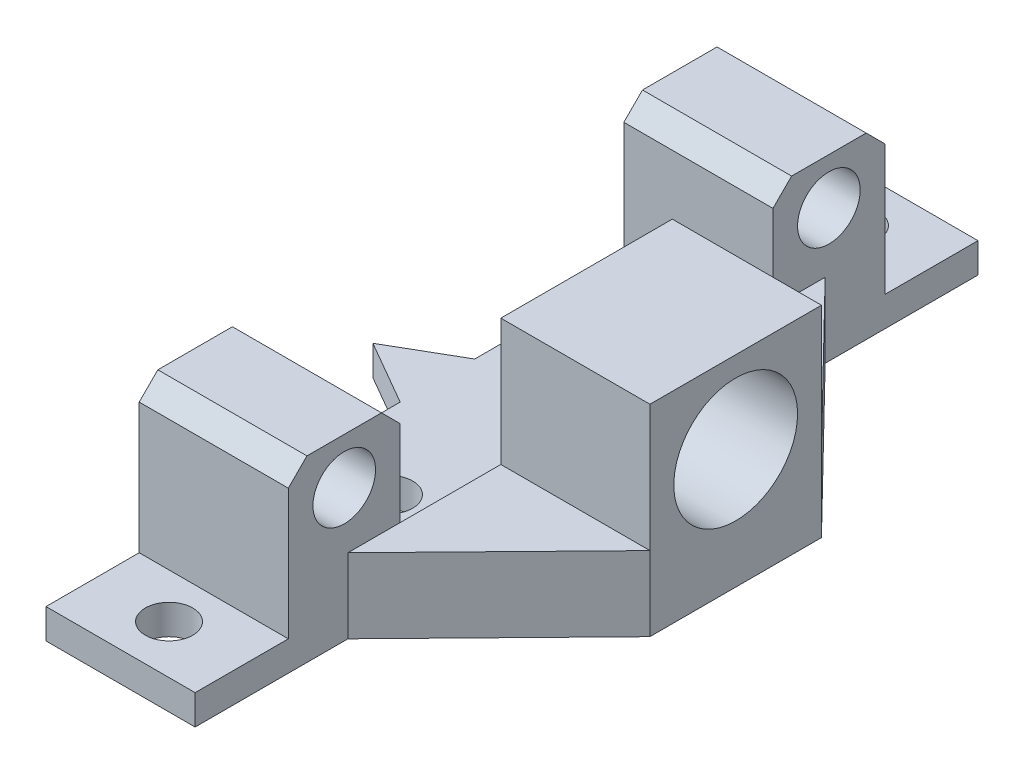
SolidWorks part; units mm, degrees
ref_plane "Front Plane" through (0, 0, 0) normal (0, 0, 1) x (1, 0, 0)
ref_plane "Top Plane" through (0, 0, 0) normal (0, 1, 0) x (1, 0, 0)
ref_plane "Right Plane" through (0, 0, 0) normal (1, 0, 0) x (0, 0, -1)
sketch "Sketch1" plane through (0, 0, 0) normal (0, 1, 0) x (1, 0, 0)
  line L1 (0, 0) -> (20, 0)
  line L2 (0, 0) -> (0, 105)
  line L3 (0, 105) -> (20, 105)
  line L4 (20, 0) -> (20, 105)
  dimension "D1" = 105
  dimension "D2" = 20
extrude "Boss-Extrude1" add sketch "Sketch1" along normal blind 4
sketch "Sketch2" plane through (0, 0, 0) normal (-1, 0, 0) x (0, 0, 1)
  line L0 (-105, 0) -> (0, 0) construction
  line L5 (-12.5, 21.5) -> (-15, 24)
  line L6 (-92.5, 0) -> (-77.5, 0)
  line L7 (-92.5, 0) -> (-92.5, 24)
  line L8 (-92.5, 24) -> (-77.5, 24)
  line L9 (-77.5, 0) -> (-77.5, 24)
  line L10 (-105, 0) -> (-92.5, 0) construction
  line L11 (-80, 24) -> (-77.5, 21.5)
  line L12 (-92.5, 21.5) -> (-90, 24)
  line L13 (-52.5, 0) -> (-52.5, 4) construction
  line L14 (-25, 24) -> (-27.5, 21.5)
  line L15 (-105, 4) -> (0, 4) construction
  line L16 (-27.5, 0) -> (-27.5, 24)
  line L17 (-12.5, 24) -> (-27.5, 24)
  line L18 (-12.5, 0) -> (-12.5, 24)
  line L19 (-12.5, 0) -> (-27.5, 0)
  circle A0 centre (-85, 17.8) radius 4.2
  circle A1 centre (-20, 17.8) radius 4.2
  point P10 (-85, 24)
  point P25 (-52.5, 4)
  point P30 (-20, 24)
  line M15 (0, 4) -> (-105, 4)
  dimension "D4" = 8.4
  dimension "D2" = 15
  dimension "D3" = 24
  dimension "D6" = 2.5
  dimension "D7" = 2.5
  dimension "D8" = 2.5
  dimension "D9" = 2.5
  dimension "D1" = 65
  dimension "D5" = 6.2
extrude "Boss-Extrude2" add sketch "Sketch2" against normal up to surface (20 mm away) contours L18 L5 L17 L14 L16 A1 M15 | L12 L7 L9 L11 L8 A0 M15 region at (0, 12.876, -20) region at (0, 12.876, -85) up to face at (20, 2, -52.5)
sketch "Sketch3" plane through (0, 0, 0) normal (0, -1, 0) x (1, 0, 0)
  line L0 (0, -57.5) -> (-8.6603, -52.5)
  line L1 (0, -105) -> (0, 0) construction
  line L2 (-8.6603, -52.5) -> (0, -47.5)
  line L3 (0, -57.5) -> (0, -47.5)
  point P6 (0, -52.5)
  dimension "D1" = 10
  dimension "D2" = 10
  dimension "D3" = 10
extrude "Boss-Extrude3" add sketch "Sketch3" against normal up to surface (4 mm away) up to face at (10, 4, -98.75)
sketch "Sketch4" plane through (0, 4, 0) normal (0, 1, 0) x (1, 0, 0)
  line L0 (10, 105) -> (10, 0) construction
  line L1 (20, 105) -> (0, 105) construction
  line L2 (0, 0) -> (20, 0) construction
  circle A0 centre (10, 98.5) radius 3.175
  circle A1 centre (10, 69) radius 3.175
  circle A2 centre (10, 36) radius 3.175
  circle A3 centre (10, 6.5) radius 3.175
  dimension "D1" = 6.35
  dimension "D2" = 6.5
  dimension "D3" = 36
  dimension "D4" = 6.5
  dimension "D5" = 36
extrude "Cut-Extrude1" cut sketch "Sketch4" against normal through all
sketch "Sketch5" plane through (20, 0, 0) normal (1, 0, 0) x (0, 0, -1)
  line L0 (0, 0) -> (105, 0) construction
  line L1 (41, 0) -> (64, 0)
  line L2 (41, 0) -> (41, 27)
  line L3 (41, 27) -> (64, 27)
  line L4 (64, 0) -> (64, 27)
  line L5 (64, 0) -> (105, 0) construction
  line L11 (15, 24) -> (90, 24) construction
  line L12 (41, 0) -> (0, 0) construction
  dimension "D1" = 23
  dimension "D2" = 3
extrude "Boss-Extrude4" add sketch "Sketch5" along normal blind 20
sketch "Sketch6" plane through (40, 0, 0) normal (1, 0, 0) x (0, 0, -1)
  line L0 (52.5, 27) -> (52.5, 0) construction
  line L1 (64, 27) -> (41, 27) construction
  line L2 (41, 0) -> (64, 0) construction
  circle A0 centre (52.5, 16) radius 8.3
  dimension "D1" = 16.6
  dimension "D2" = 11
extrude "Cut-Extrude2" cut sketch "Sketch6" against normal through all
sketch "Sketch11" plane through (0, 0, 0) normal (0, -1, 0) x (1, 0, 0)
  line L0 (40, -64) -> (20, -84.5)
  line L1 (20, -64) -> (20, -105) construction
  line L2 (40, -64) -> (20, -64)
  line L3 (20, -64) -> (20, -84.5)
  line L4 (40, -41) -> (20, -41)
  line L5 (20, -41) -> (20, -20.5)
  line L7 (20, -20.5) -> (40, -41)
  line L8 (20, 0) -> (20, -41) construction
extrude "Boss-Extrude5" add sketch "Sketch11" against normal blind 10
equation "\"8mm hole\" = 8.4mm"
equation "\"D4@Sketch2\"= \"8mm hole\""
equation "\"22mm hole\"= 23mm"
equation "\"15mm hole\"= 15.8mm"
equation "\"bed height offset\"= 3mm"
equation "\"D3@Sketch2\"= 21 + \"bed height offset\""
